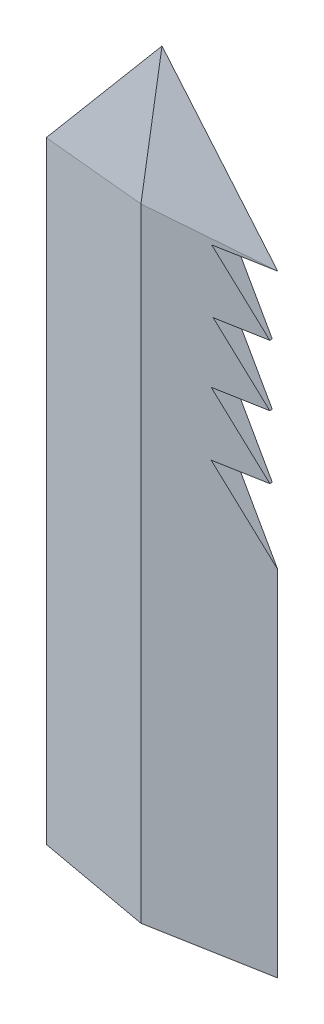
SolidWorks part; units mm, degrees
ref_plane "Front Plane" through (0, 0, 0) normal (0, 0, 1) x (1, 0, 0)
ref_plane "Top Plane" through (0, 0, 0) normal (0, 1, 0) x (1, 0, 0)
ref_plane "Right Plane" through (0, 0, 0) normal (1, 0, 0) x (0, 0, -1)
sketch "Sketch1" plane through (0, 0, 0) normal (0, 0, 1) x (1, 0, 0)
  line L0 (101.7924, 735.6565) -> (49.4049, 673.5573)
  line L1 (49.4049, 673.5573) -> (49.4049, 396.4974)
  line L2 (49.4049, 396.4974) -> (154.1799, 396.4974)
  line L3 (154.1799, 396.4974) -> (154.1799, 556.6364)
  line L4 (154.1799, 673.5573) -> (101.7924, 735.6565)
  line L5 (154.1799, 673.5573) -> (128.876, 673.5573)
  line L6 (128.876, 673.5573) -> (151.1488, 645.2298)
  line L7 (151.1488, 645.2298) -> (129.452, 645.2298)
  line L8 (129.452, 645.2298) -> (151.1488, 617.6349)
  line L9 (151.1488, 617.6349) -> (128.684, 617.6349)
  line L10 (128.684, 617.6349) -> (151.1488, 589.0632)
  line L11 (151.1488, 589.0632) -> (128.684, 589.0632)
  line L12 (128.684, 589.0632) -> (154.1799, 556.6364)
  point P2 (101.7924, 396.4974)
  dimension "D1" = 104.775
extrude "Boss-Extrude1" add sketch "Sketch1" along normal blind 9.525 and the other way blind 9.525
sketch "Sketch2" plane through (0, 396.4974, 0) normal (0, -1, 0) x (-1, 0, 0)
  line L0 (-49.4049, 0) -> (-101.7924, -9.525)
  line L1 (-49.4049, 9.525) -> (-49.4049, -9.525) construction
  line L2 (-49.4049, -9.525) -> (-154.1799, -9.525) construction
  line L3 (-101.7924, -9.525) -> (-154.1799, 0)
  line L4 (-154.1799, 9.525) -> (-154.1799, -9.525) construction
  line L5 (-154.1799, 0) -> (-159.6573, 0)
  line L6 (-159.6573, 0) -> (-159.6573, -13.6491)
  line L7 (-159.6573, -13.6491) -> (-44.1585, -13.6491)
  line L8 (-44.1585, -13.6491) -> (-44.1585, 0)
  line L9 (-44.1585, 0) -> (-49.4049, 0)
extrude "Cut-Extrude1" cut sketch "Sketch2" against normal through all
sketch "Sketch3" plane through (0, 396.4974, 0) normal (0, -1, 0) x (1, 0, 0)
  line L0 (49.4049, 0) -> (101.7924, -9.525)
  line L1 (101.7924, -9.525) -> (154.1799, 0)
  line L2 (154.1799, 0) -> (159.5806, 0)
  line L3 (159.5806, 0) -> (159.5806, -14.5007)
  line L4 (159.5806, -14.5007) -> (43.682, -14.5007)
  line L5 (43.682, -14.5007) -> (43.682, 0)
  line L6 (43.682, 0) -> (49.4049, 0)
extrude "Cut-Extrude2" cut sketch "Sketch3" against normal through all
sketch "Sketch4" plane through (4.9338, 0, 27.1357) normal (0.1789, 0, 0.9839) x (0.9839, 0, -0.1789)
  line L0 (98.4466, 735.6565) -> (98.4466, 396.4974) construction
  point P0 (98.4466, 678.5065)
  dimension "D1" = 57.15
ref_plane "Plane1" through (26.4305, 22.297, 133.782) normal (0.1913, 0.1614, 0.9682) x (0.9815, -0.0314, -0.1887)
sketch "Sketch5" plane through (26.4305, 22.297, 133.782) normal (0.1913, 0.1614, 0.9682) x (0.9815, -0.0314, -0.1887)
  line L1 (40.4892, 768.9526) -> (138.0076, 768.9526)
  line L2 (40.4892, 768.9526) -> (40.4892, 632.533)
  line L3 (40.4892, 632.533) -> (138.0076, 632.533)
  line L4 (138.0076, 768.9526) -> (138.0076, 632.533)
extrude "Cut-Extrude3" cut sketch "Sketch5" along normal through all
ref_plane "Plane2" through (-18.9819, 16.0133, 96.0799) normal (-0.1913, 0.1614, 0.9682) x (0.9815, 0.0314, 0.1887)
sketch "Sketch6" plane through (-18.9819, 16.0133, 96.0799) normal (-0.1913, 0.1614, 0.9682) x (0.9815, 0.0314, 0.1887)
  line L1 (61.3232, 620.6538) -> (136.4239, 620.6538)
  line L2 (61.3232, 620.6538) -> (61.3232, 774.9318)
  line L3 (61.3232, 774.9318) -> (136.4239, 774.9318)
  line L4 (136.4239, 620.6538) -> (136.4239, 774.9318)
extrude "Cut-Extrude4" cut sketch "Sketch6" along normal through all
mirror "Mirror1" about plane through (0, 0, 0) normal (0, 0, 1) of "Cut-Extrude4", "Cut-Extrude3"
sketch "Sketch7" plane through (0, 396.4974, 0) normal (0, -1, 0) x (1, 0, 0)
  circle A0 centre (101.7924, 0) radius 4.7625
  dimension "D1" = 9.525
extrude "Cut-Extrude5" cut sketch "Sketch7" against normal blind 254
